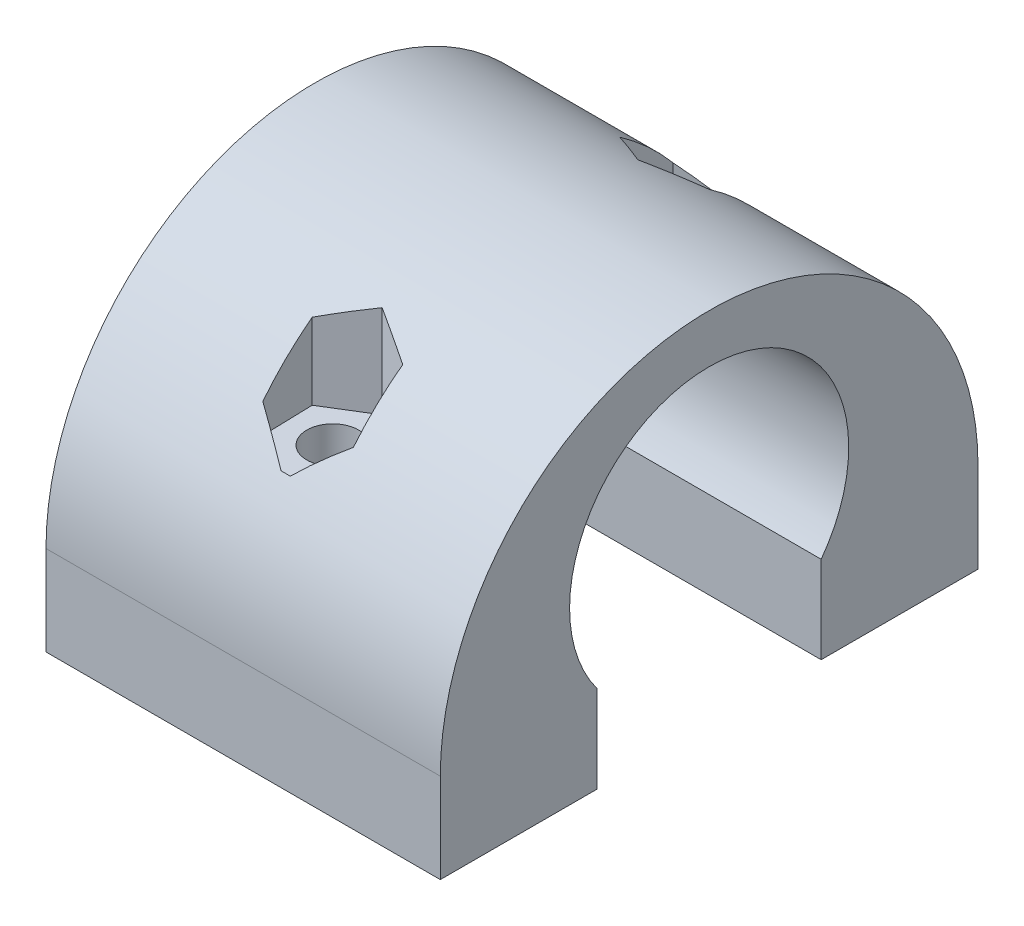
SolidWorks part; units mm, degrees
ref_plane "Front Plane" through (0, 0, 0) normal (0, 0, 1) x (1, 0, 0)
ref_plane "Top Plane" through (0, 0, 0) normal (0, 1, 0) x (1, 0, 0)
ref_plane "Right Plane" through (0, 0, 0) normal (1, 0, 0) x (0, 0, -1)
sketch "Sketch1" plane through (0, 0, 0) normal (0, 1, 0) x (1, 0, 0)
  line L1 (-21.0811, 11.7568) -> (0.9189, 11.7568)
  line L2 (-21.0811, 11.7568) -> (-21.0811, -18.2432)
  line L3 (-21.0811, -18.2432) -> (0.9189, -18.2432)
  line L4 (0.9189, 11.7568) -> (0.9189, -18.2432)
  dimension "D1" = 30
  dimension "D2" = 22
extrude "Boss-Extrude1" add sketch "Sketch1" along normal blind 20
fillet "Fillet2" 2 edges at (-10.0811, 20, -11.7568) (-10.0811, 20, 18.2432) type full round first side face at (-10.0811, 10, -11.7568) second side face at (-10.0811, 10, 18.2432) middle face at (-10.0811, 20, 3.2432)
sketch "Sketch7" plane through (0, 0, 0) normal (0, -1, 0) x (1, 0, 0)
  line L1 (-21.0811, -11.7568) -> (0.9189, -11.7568)
  line L2 (-21.0811, -11.7568) -> (-21.0811, -3.4568)
  line L3 (-21.0811, -3.4568) -> (0.9189, -3.4568)
  line L4 (0.9189, -11.7568) -> (0.9189, -3.4568)
  line L8 (-21.0811, 9.9432) -> (0.9189, 9.9432)
  line L9 (-21.0811, 9.9432) -> (-21.0811, 18.2432)
  line L10 (-21.0811, 18.2432) -> (0.9189, 18.2432)
  line L11 (0.9189, 9.9432) -> (0.9189, 18.2432)
  line L15 (-21.0811, -11.7568) -> (-21.0811, 18.2432) construction
  line L16 (0.9189, 18.2432) -> (0.9189, -11.7568) construction
  point P4 (-21.0811, -3.4961)
  point P5 (0.9189, -3.492)
  point P6 (-21.0811, 9.9811)
  point P7 (-21.0811, -11.7568)
  point P9 (0, 0)
  point P10 (-21.0811, 18.2432)
  point P11 (0, 0)
  point P13 (0.9189, 9.9733)
  point P15 (0, 0)
  dimension "D1" = 8.3
  dimension "D2" = 8.3
extrude "Boss-Extrude2" add sketch "Sketch7" against normal blind 3.988
sketch "Sketch4" plane through (0, 0, 0) normal (0, -1, 0) x (-1, 0, 0)
  line L1 (-0.9189, -18.2432) -> (-0.9189, 11.7568) construction
  line L3 (-0.9189, -18.2432) -> (-0.9189, 11.7568) construction
  line L6 (21.0811, -18.2432) -> (-0.9189, -18.2432) construction
  circle A0 centre (10.0811, 6.7568) radius 1.45
  circle A1 centre (10.0811, -13.2432) radius 1.45
  dimension "D1" = 20
  dimension "D3" = 5
  dimension "D2" = 11
  dimension "D6" = 11
sketch "Sketch3" plane through (-21.0811, 0, 0) normal (-1, 0, 0) x (0, 0, 1)
  line L2 (18.2432, 5) -> (18.2432, 0) construction
  circle A0 centre (3.2432, 9.5) radius 7.7866
  arc A1 (18.2432, 5) -> (-11.7568, 5) centre (3.2432, 5) ccw construction
  point P5 (0, 0)
  dimension "D2" = 4.5
  dimension "D1" = 15
extrude "Cut-Extrude2" cut sketch "Sketch3" against normal blind 25
extrude "Cut-Extrude3" cut sketch "Sketch4" against normal blind 19
sketch "Sketch9" plane through (0, 0, 0) normal (0, -1, 0) x (1, 0, 0)
  line L1 (-21.0811, -3.0068) -> (0.9189, -3.0068)
  line L2 (-21.0811, -3.0068) -> (-21.0811, 9.4932)
  line L3 (-21.0811, 9.4932) -> (0.9189, 9.4932)
  line L4 (0.9189, -3.0068) -> (0.9189, 9.4932)
  line L5 (0.9189, -11.7568) -> (-21.0811, -11.7568) construction
  line L7 (-21.0811, -11.7568) -> (-21.0811, 18.2432) construction
  point P4 (-21.0811, 9.4932)
  dimension "D1" = 12.5
  dimension "D2" = 8.75
  dimension "D3" = 22
extrude "Cut-Extrude5" cut sketch "Sketch9" against normal blind 5
ref_plane "Plane1" through (0, 15, 0) normal (0, -1, 0) x (-1, 0, 0)
sketch "Sketch11" plane through (0, 15, 0) normal (0, -1, 0) x (-1, 0, 0)
  line L1 (7.5847, -14.5914) -> (10.0004, -16.0792)
  line L2 (10.0004, -16.0792) -> (12.4968, -14.7311)
  line L3 (12.4968, -14.7311) -> (12.5775, -11.8951)
  line L4 (12.5775, -11.8951) -> (10.1617, -10.4073)
  line L5 (10.1617, -10.4073) -> (7.6654, -11.7554)
  line L6 (7.6654, -11.7554) -> (7.5847, -14.5914)
  line L7 (7.5629, 5.2456) -> (10.1306, 3.8204)
  line L8 (10.1306, 3.8204) -> (12.6488, 5.3315)
  line L9 (12.6488, 5.3315) -> (12.5993, 8.2679)
  line L10 (12.5993, 8.2679) -> (10.0315, 9.6931)
  line L11 (10.0315, 9.6931) -> (7.5133, 8.182)
  line L12 (7.5133, 8.182) -> (7.5629, 5.2456)
  circle A0 centre (10.0811, -13.2432) radius 2.457 construction
  circle A1 centre (10.0811, 6.7568) radius 2.5434 construction
extrude "Cut-Extrude6" cut sketch "Sketch11" against normal blind 5 and the other way blind 2
